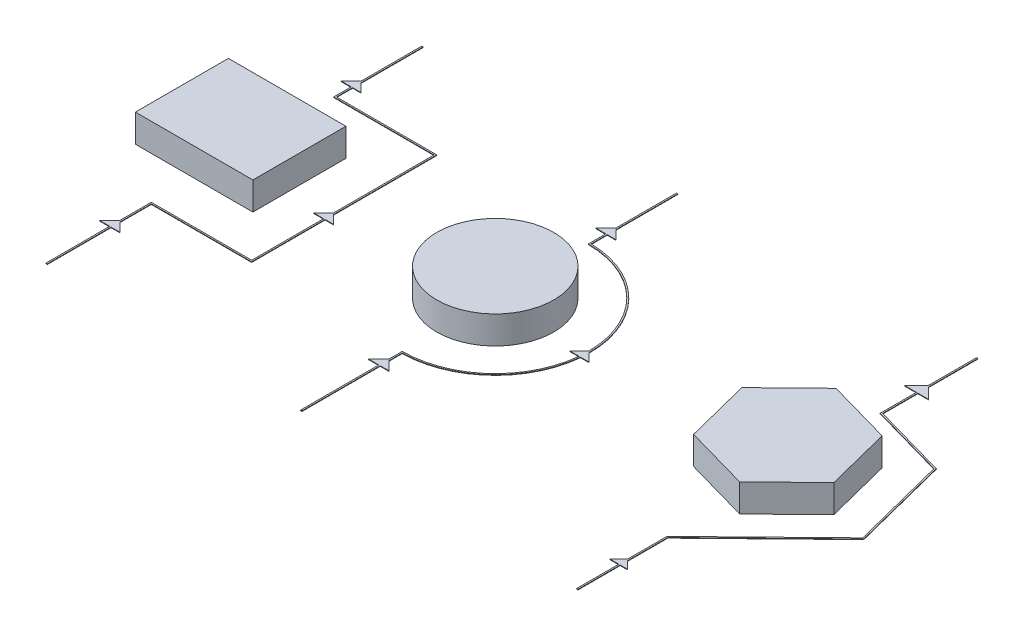
SolidWorks part; units mm, degrees
ref_plane "Front Plane" through (0, 0, 0) normal (0, 0, 1) x (1, 0, 0)
ref_plane "Top Plane" through (0, 0, 0) normal (0, 1, 0) x (1, 0, 0)
ref_plane "Right Plane" through (0, 0, 0) normal (1, 0, 0) x (0, 0, -1)
sketch "Sketch1" plane through (0, 0, 0) normal (0, 1, 0) x (1, 0, 0)
  line L0 (-158.1147, -69.9311) -> (-158.1147, -32.1067)
  line L1 (-179.226, -16.7131) -> (-137.0034, -16.7131)
  line L2 (-179.226, -16.7131) -> (-179.226, 16.7131)
  line L3 (-179.226, 16.7131) -> (-137.0034, 16.7131)
  line L4 (-137.0034, -16.7131) -> (-137.0034, 16.7131)
  line L5 (-179.226, -16.7131) -> (-137.0034, 16.7131) construction
  line L6 (-179.226, 16.7131) -> (-137.0034, -16.7131) construction
  line L7 (55.637, 16.7131) -> (32.5866, 23.2114)
  line L8 (32.5866, 23.2114) -> (15.4337, 6.4983)
  line L9 (15.4337, 6.4983) -> (21.3312, -16.7131)
  line L10 (21.3312, -16.7131) -> (44.3816, -23.2114)
  line L11 (44.3816, -23.2114) -> (61.5345, -6.4983)
  line L12 (61.5345, -6.4983) -> (55.637, 16.7131)
  line L13 (-158.1147, -32.1067) -> (-122.0496, -32.1067)
  line L14 (-122.0496, -32.1067) -> (-122.0496, 33.4262)
  line L15 (-122.0496, 33.4262) -> (-158.1147, 33.4262)
  line L16 (-158.1147, 33.4262) -> (-158.1147, 65.0931)
  line L17 (-66.6325, -69.9311) -> (-66.6325, -33.4262)
  line L18 (-66.6325, 33.4262) -> (-66.6325, 65.0931)
  line L19 (38.4841, -75.8638) -> (38.4841, -43.4276)
  line L20 (38.4841, -43.4276) -> (74.1067, -8.7184)
  line L21 (74.1067, -8.7184) -> (65.3831, 25.616)
  line L22 (65.3831, 25.616) -> (38.4841, 33.1993)
  line L23 (38.4841, 33.1993) -> (38.4841, 67.8221)
  line L24 (-158.1147, -43.4276) -> (-161.7416, -47.0545)
  line L25 (-161.7416, -47.0545) -> (-154.4879, -47.0545)
  line L26 (-154.4879, -47.0545) -> (-158.1147, -43.4276)
  line L27 (-122.0844, -2.6133) -> (-125.7113, -6.2402)
  line L28 (-125.7113, -6.2402) -> (-118.4575, -6.2402)
  line L29 (-118.4575, -6.2402) -> (-122.0844, -2.6133)
  line L30 (-158.1699, 43.3391) -> (-161.7896, 39.7194)
  line L31 (-161.7896, 39.7194) -> (-154.5501, 39.7194)
  line L32 (-154.5501, 39.7194) -> (-158.1699, 43.3391)
  line L33 (-66.6208, -38.2276) -> (-70.2476, -41.8545)
  line L34 (-70.2476, -41.8545) -> (-62.9939, -41.8545)
  line L35 (-62.9939, -41.8545) -> (-66.6208, -38.2276)
  line L36 (-66.6325, 43.3391) -> (-70.2476, 39.724)
  line L37 (-70.2476, 39.724) -> (-62.9939, 39.724)
  line L38 (-62.9939, 39.724) -> (-66.6325, 43.3391)
  line L39 (-33.2068, 0.183) -> (-36.5568, -3.1888)
  line L40 (-36.5568, -3.1888) -> (-29.8131, -3.1888)
  line L41 (-29.8131, -3.1888) -> (-33.2068, 0.183)
  line L42 (38.4841, 50.5107) -> (34.1822, 46.2088)
  line L43 (38.4841, 50.5107) -> (42.7861, 46.2088)
  line L44 (42.7861, 46.2088) -> (34.1822, 46.2088)
  line L45 (38.4841, -57.6638) -> (35.4035, -60.7444)
  line L46 (35.4035, -60.7444) -> (41.5647, -60.7444)
  line L47 (41.5647, -60.7444) -> (38.4841, -57.6638)
  circle A0 centre (-66.6325, 0) radius 21.0241
  circle A1 centre (38.4841, 0) radius 20.7404 construction
  arc A2 (-66.6325, 33.4262) -> (-66.6325, -33.4262) centre (-66.6325, 0) cw
  point P0 (-158.1147, 0)
extrude "Boss-Extrude1" add sketch "Sketch1" along normal blind 10 contours L1 L4 L3 L2 | A0 | L11 L12 L7 L8 L9 L10 region at (-158.1147, 0, 0) region at (38.4841, 0, 0) region at (-66.6325, 0, 0)
extrude "Boss-Extrude3" add sketch "Sketch1<5>" along normal blind 0.2 separate body contours L24 L25 L0 | L25 L26 L0 | L31 L32 L30 | L27 L28 L29 | L35 L33 L34 | L40 L41 L39 | L37 L38 L36 | L44 L42 L43 | L46 L47 L45 region at (-156.9058, 0, 45.8455) region at (-159.3237, 0, 45.8455)
sketch "Sketch1<5>" plane through (0, 0, 0) normal (0, 1, 0) x (1, 0, 0) same geometry as "Sketch1"
extrude "Extrude-Thin1" add sketch "Sketch1<6>" along normal blind 0.2 thin contours L0 L13 L14 L15 L16 | L17 A2 L18 | L19 L20 L21 L22 L23 thin type one direction wall 0.5
sketch "Sketch1<6>" plane through (0, 0, 0) normal (0, 1, 0) x (1, 0, 0) same geometry as "Sketch1"
